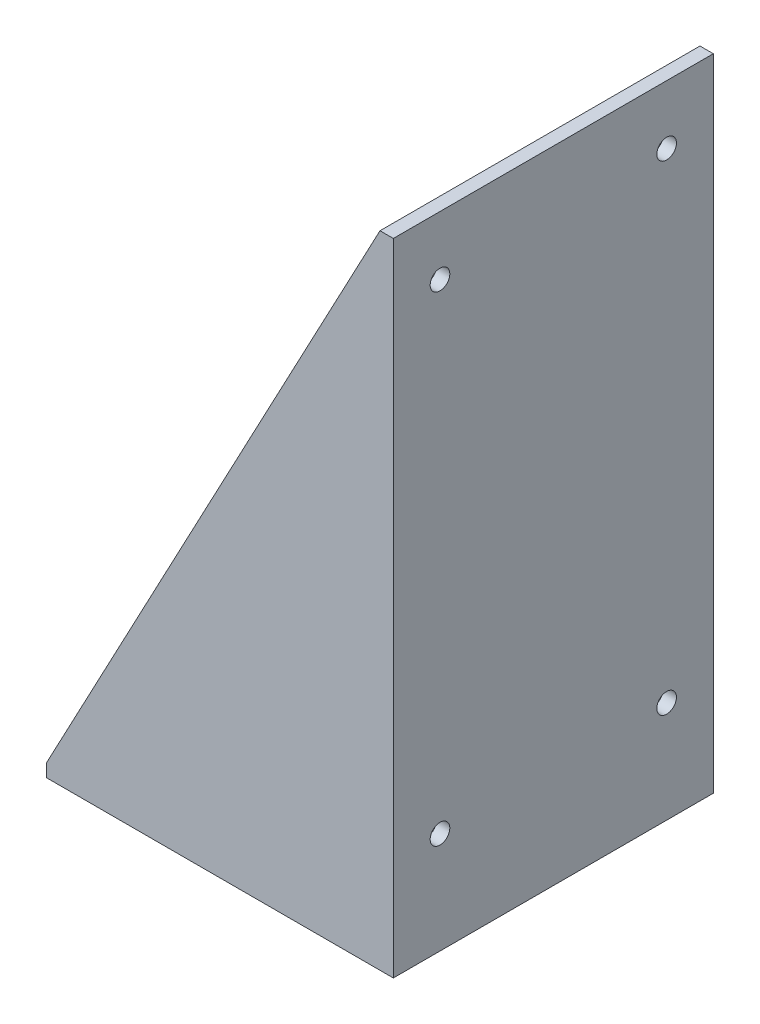
SolidWorks part; units mm, degrees
ref_plane "Front Plane" through (0, 0, 0) normal (0, 0, 1) x (1, 0, 0)
ref_plane "Top Plane" through (0, 0, 0) normal (0, 1, 0) x (1, 0, 0)
ref_plane "Right Plane" through (0, 0, 0) normal (1, 0, 0) x (0, 0, -1)
sketch "Sketch1" plane through (0, 0, 0) normal (0, 1, 0) x (1, 0, 0)
  line L2 (-49.4299, -37.5879) -> (33.1201, -37.5879)
  line L3 (-49.4299, -37.5879) -> (-49.4299, 38.6121)
  line L4 (-49.4299, 38.6121) -> (33.1201, 38.6121)
  line L5 (33.1201, -37.5879) -> (33.1201, 38.6121)
  dimension "D1" = 76.2
  dimension "D2" = 82.55
extrude "Boss-Extrude1" add sketch "Sketch1" along normal blind 3.175
sketch "Sketch2" plane through (33.1201, 0, 0) normal (1, 0, 0) x (0, 0, -1)
  line L0 (-37.5879, 3.175) -> (38.6121, 3.175) construction
  line L1 (-37.5879, 3.175) -> (38.6121, 3.175)
  line L2 (-37.5879, 3.175) -> (-37.5879, 152.527)
  line L3 (-37.5879, 152.527) -> (38.6121, 152.527)
  line L4 (38.6121, 3.175) -> (38.6121, 152.527)
  point P5 (-37.5879, 0)
  dimension "D1" = 76.2
  dimension "D2" = 149.352
extrude "Boss-Extrude2" add sketch "Sketch2" against normal blind 3.175
sketch "Sketch3" plane through (29.9451, 0, 0) normal (-1, 0, 0) x (0, 0, 1)
  line L0 (-27.4996, 24.2062) -> (26.4754, 24.2062) construction
  line L1 (-0.5121, 152.527) -> (-0.5121, 3.175) construction
  line L2 (-38.6121, 152.527) -> (37.5879, 152.527) construction
  line L3 (37.5879, 3.175) -> (-38.6121, 3.175) construction
  line L4 (-27.4996, 138.5062) -> (26.4754, 138.5062) construction
  circle A0 centre (-27.4996, 24.2062) radius 2.3367
  circle A1 centre (26.4754, 24.2062) radius 2.3367
  circle A2 centre (-27.4996, 138.5062) radius 2.3367
  circle A3 centre (26.4754, 138.5062) radius 2.3367
  point P10 (-0.5121, 24.2062)
  point P15 (-0.5121, 77.851)
  dimension "D3" = 4.6735
  dimension "D1" = 53.975
  dimension "D2" = 21.0312
  dimension "D4" = 114.3
extrude "Cut-Extrude1" cut sketch "Sketch3" against normal through all
sketch "Sketch4" plane through (0, 3.175, 0) normal (0, 1, 0) x (1, 0, 0)
  line L0 (29.9451, 0.5121) -> (-49.4299, 0.5121) construction
  line L1 (29.9451, -37.5879) -> (29.9451, 38.6121) construction
  line L2 (-49.4299, 38.6121) -> (-49.4299, -37.5879) construction
  line L3 (-43.0799, 25.9121) -> (-43.0799, -24.8879) construction
  circle A0 centre (-43.0799, 25.9121) radius 4.3656
  circle A1 centre (-17.6799, 25.9121) radius 4.3656
  circle A2 centre (-17.6799, -24.8879) radius 4.3656
  circle A3 centre (-43.0799, -24.8879) radius 4.3656
  point P14 (-9.7424, 0.5121)
  dimension "D1" = 8.7312
  dimension "D2" = 25.4
  dimension "D3" = 50.8
  dimension "D4" = 6.35
extrude "Cut-Extrude2" cut sketch "Sketch4" against normal through all
sketch "Sketch5" plane through (0, 0, 37.5879) normal (0, 0, 1) x (1, 0, 0)
  line L0 (-49.4299, 3.175) -> (29.9451, 152.527)
  line L1 (29.9451, 152.527) -> (29.9451, 3.175)
  line L2 (29.9451, 3.175) -> (-49.4299, 3.175)
extrude "Boss-Extrude3" add sketch "Sketch5" against normal blind 2.54
sketch "Sketch7" plane through (0, 0, -38.6121) normal (0, 0, -1) x (-1, 0, 0)
  line L0 (-29.9451, 152.527) -> (49.4299, 3.175)
  line L1 (49.4299, 3.175) -> (-29.9451, 3.175)
  line L2 (-29.9451, 3.175) -> (-29.9451, 152.527)
extrude "Boss-Extrude4" add sketch "Sketch7" against normal blind 2.54
